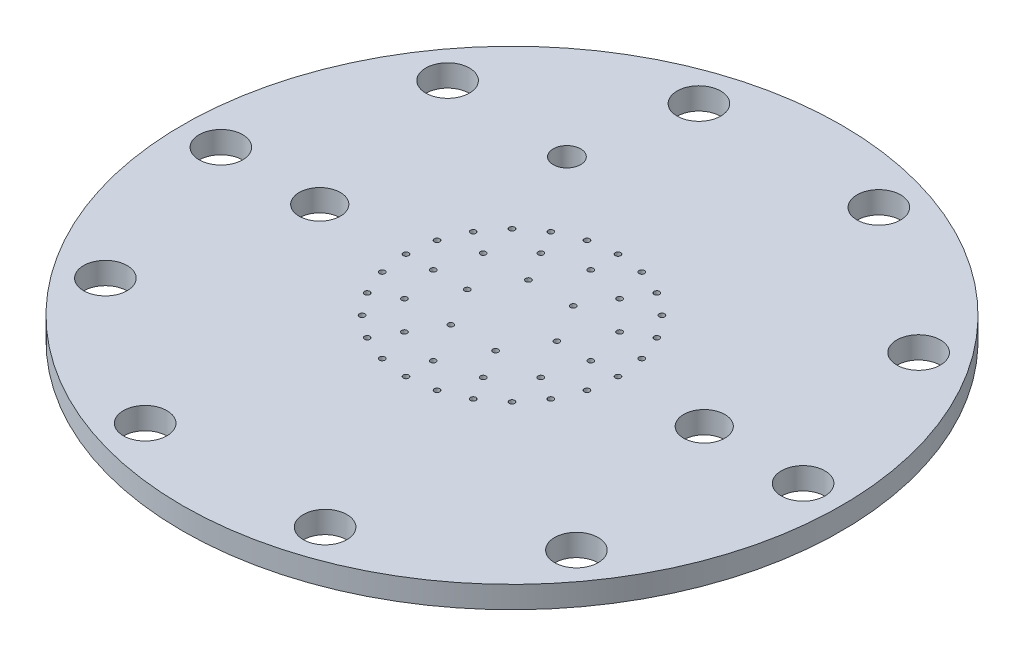
SolidWorks part; units mm, degrees
ref_plane "Front Plane" through (0, 0, 0) normal (0, 0, 1) x (1, 0, 0)
ref_plane "Top Plane" through (0, 0, 0) normal (0, 1, 0) x (1, 0, 0)
ref_plane "Right Plane" through (0, 0, 0) normal (1, 0, 0) x (0, 0, -1)
sketch "Sketch1" plane through (0, 0, 0) normal (0, 0, 1) x (1, 0, 0)
  line L0 (0, 0) -> (0, -5.08)
  line L2 (76.2, -5.08) -> (76.2, 0)
  line L3 (76.2, 0) -> (0, 0)
  line L4 (0, -5.08) -> (54.8259, -5.08)
  line L5 (54.8259, -5.08) -> (54.8259, -2.3876)
  line L6 (54.8259, -2.3876) -> (58.8899, -2.3876)
  line L7 (58.8899, -2.3876) -> (58.8899, -5.08)
  line L8 (58.8899, -5.08) -> (76.2, -5.08)
  dimension "D1" = 5.08
  dimension "D2" = 76.2
  dimension "D3" = 58.8899
  dimension "D4" = 4.064
  dimension "D5" = 2.6924
revolve "Revolve1" add sketch "Sketch1" angle 360 about L0
ref_axis "Axis1" through (0, -5.334, 0) along (0, 1, 0)
sketch "Sketch2" plane through (0, 0, 0) normal (0, 1, 0) x (1, 0, 0)
  line L0 (0, 0) -> (67.31, 0) construction
  dimension "D1" = 67.31
hole_wizard "3/8 Clearance Hole1" positions "3DSketch2" profile "Sketch3" hole size "3/8" standard "ANSI Inch" end condition through all
sketch3d "3DSketch2"
  point P0 (67.31, 0, 0)
sketch "Sketch3" plane through (67.31, 0, 0) normal (1, 0, 0) x (0, 0, 1)
  line L0 (0, 0) -> (0, 5.08)
  line L1 (0, 5.08) -> (5.0419, 5.08)
  line L2 (5.0419, 5.08) -> (5.0419, 0)
  line L5 (5.0419, 0) -> (0, 0)
  line L11 (0, -6.35) -> (0, 107.95) construction
  dimension "Thru Hole Dia." = 10.0838
  dimension "Thru Hole Depth" = 5.08
pattern_circular "CirPattern1" count 10 over 360 about axis through (0, -5.334, 0) along (0, 1, 0) of "3/8 Clearance Hole1"
hole_wizard "3/8 (0.375) Diameter Hole1" positions "3DSketch3" profile "Sketch4" hole size "3/8" standard "ANSI Inch" end condition through all
sketch3d "3DSketch3"
  line L1 (0, 0, 0) -> (67.31, 0, 0) construction
  point P18 (44.45, 0, 0)
  point P38 (-44.45, 0, 0)
  dimension "D1" = 44.45
  dimension "D2" = 44.45
sketch "Sketch4" plane through (44.45, 0, 0) normal (1, 0, 0) x (0, 0, 1)
  line L0 (0, 0) -> (0, 5.08)
  line L1 (0, 5.08) -> (4.7625, 5.08)
  line L2 (4.7625, 5.08) -> (4.7625, 0)
  line L5 (4.7625, 0) -> (0, 0)
  line L11 (0, -6.35) -> (0, 107.95) construction
  dimension "Thru Hole Dia." = 9.525
  dimension "Thru Hole Depth" = 5.08
sketch "Sketch5" plane through (0, 0, 0) normal (0, 1, 0) x (1, 0, 0)
  line L0 (0, 0) -> (0, 38.1) construction
  line L1 (0, 38.1) -> (0, 0) construction
  line L2 (0, 0) -> (-25.4, 38.1) construction
  line L3 (-25.4, 38.1) -> (0, 38.1) construction
  dimension "D1" = 38.1
  dimension "D2" = 25.4
hole_wizard "1/4 (0.25) Diameter Hole1" positions "3DSketch4" profile "Sketch6" hole size "1/4" standard "ANSI Inch" end condition through all
sketch3d "3DSketch4"
  point P0 (-25.4, 0, -38.1)
sketch "Sketch6" plane through (-25.4, 0, -38.1) normal (1, 0, 0) x (0, 0, 1)
  line L0 (0, 0) -> (0, 5.08)
  line L1 (0, 5.08) -> (3.175, 5.08)
  line L2 (3.175, 5.08) -> (3.175, 0)
  line L5 (3.175, 0) -> (0, 0)
  line L11 (0, -6.35) -> (0, 107.95) construction
  dimension "Thru Hole Dia." = 6.35
  dimension "Thru Hole Depth" = 5.08
sketch "Sketch7" plane through (0, 0, 0) normal (0, 1, 0) x (1, 0, 0)
  line L0 (0, 0) -> (67.31, 0) construction
  line L1 (0, 0) -> (10.3632, 0) construction
  line L2 (0, 0) -> (5.1816, -8.9748) construction
  line L3 (0, 0) -> (18.2118, 0) construction
  line L4 (0, 0) -> (24.511, 0) construction
  circle A0 centre (10.3632, 0) radius 0.635
  circle A1 centre (18.2118, 0) radius 0.635
  circle A2 centre (24.511, 0) radius 0.635
  circle A3 centre (5.1816, -8.9748) radius 0.635
  circle A4 centre (-5.1816, -8.9748) radius 0.635
  circle A5 centre (-10.3632, 0) radius 0.635
  circle A6 centre (-5.1816, 8.9748) radius 0.635
  circle A7 centre (5.1816, 8.9748) radius 0.635
  circle A8 centre (15.7719, -9.1059) radius 0.635
  circle A9 centre (9.1059, -15.7719) radius 0.635
  circle A10 centre (0, -18.2118) radius 0.635
  circle A11 centre (-9.1059, -15.7719) radius 0.635
  circle A12 centre (-15.7719, -9.1059) radius 0.635
  circle A13 centre (-18.2118, 0) radius 0.635
  circle A14 centre (-15.7719, 9.1059) radius 0.635
  circle A15 centre (-9.1059, 15.7719) radius 0.635
  circle A16 centre (0, 18.2118) radius 0.635
  circle A17 centre (9.1059, 15.7719) radius 0.635
  circle A18 centre (15.7719, 9.1059) radius 0.635
  circle A19 centre (23.6758, -6.3439) radius 0.635
  circle A20 centre (21.2271, -12.2555) radius 0.635
  circle A21 centre (17.3319, -17.3319) radius 0.635
  circle A22 centre (12.2555, -21.2271) radius 0.635
  circle A23 centre (6.3439, -23.6758) radius 0.635
  circle A24 centre (0, -24.511) radius 0.635
  circle A25 centre (-6.3439, -23.6758) radius 0.635
  circle A26 centre (-12.2555, -21.2271) radius 0.635
  circle A27 centre (-17.3319, -17.3319) radius 0.635
  circle A28 centre (-21.2271, -12.2555) radius 0.635
  circle A29 centre (-23.6758, -6.3439) radius 0.635
  circle A30 centre (-24.511, 0) radius 0.635
  circle A31 centre (-23.6758, 6.3439) radius 0.635
  circle A32 centre (-21.2271, 12.2555) radius 0.635
  circle A33 centre (-17.3319, 17.3319) radius 0.635
  circle A34 centre (-12.2555, 21.2271) radius 0.635
  circle A35 centre (-6.3439, 23.6758) radius 0.635
  circle A36 centre (0, 24.511) radius 0.635
  circle A37 centre (6.3439, 23.6758) radius 0.635
  circle A38 centre (12.2555, 21.2271) radius 0.635
  circle A39 centre (17.3319, 17.3319) radius 0.635
  circle A40 centre (21.2271, 12.2555) radius 0.635
  circle A41 centre (23.6758, 6.3439) radius 0.635
  dimension "D1" = 1.27
  dimension "D3" = 1.27
  dimension "D4" = 1.27
  dimension "D2" = 10.3632
  dimension "D5" = 18.2118
  dimension "D6" = 24.511
  dimension "D8" = 60
  dimension "D9" = 10.3632
  dimension "D11" = 18.2118
  dimension "D13" = 24.511
  dimension "D7" = 6
  dimension "D10" = 12
  dimension "D12" = 24
extrude "Cut-Extrude1" cut sketch "Sketch7" against normal through all both and the other way through all
